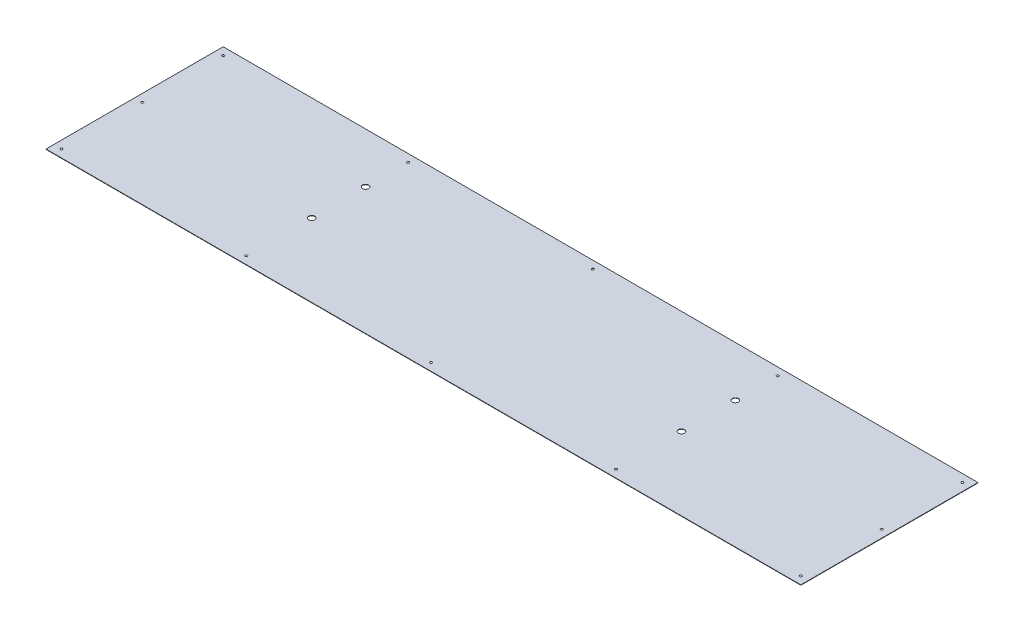
SolidWorks part; units mm, degrees
ref_plane "Front Plane" through (0, 0, 0) normal (0, 0, 1) x (1, 0, 0)
ref_plane "Top Plane" through (0, 0, 0) normal (0, 1, 0) x (1, 0, 0)
ref_plane "Right Plane" through (0, 0, 0) normal (1, 0, 0) x (0, 0, -1)
sketch "Sketch1" plane through (0, 0, 0) normal (0, 1, 0) x (1, 0, 0)
  line L1 (980, 230) -> (-980, 230)
  line L2 (980, 230) -> (980, -230)
  line L3 (980, -230) -> (-980, -230)
  line L4 (-980, 230) -> (-980, -230)
  line L5 (980, 230) -> (-980, -230) construction
  line L6 (980, -230) -> (-980, 230) construction
  point P0 (0, 0)
  dimension "D1" = 460
  dimension "D2" = 1960
extrude "Boss-Extrude1" add sketch "Sketch1" along normal blind 1
ref_plane "Plane1" through (0, 1, 0) normal (0, 1, 0) x (1, 0, 0)
sketch "Sketch2" plane through (0, 1, 0) normal (0, 1, 0) x (1, 0, 0)
  line L0 (0, -210) -> (-960, -210) construction
  line L1 (960, -210) -> (0, -210) construction
  line L2 (960, 210) -> (0, 210) construction
  line L3 (0, 210) -> (-960, 210) construction
  line L4 (-980, 230) -> (-980, -230)
  line L5 (-980, -230) -> (980, -230)
  line L6 (980, -230) -> (980, 230)
  line L7 (980, 230) -> (-980, 230)
  line L8 (-980, 230) -> (-980, -230) construction
  line L9 (-480, 100) -> (480, 100) construction
  line L10 (-480, 100) -> (-480, -40) construction
  line L11 (-980, 100) -> (980, 100) construction
  line L12 (-480, -40) -> (480, -40) construction
  line L13 (-980, -40) -> (980, -40) construction
  line L14 (-980, -230) -> (980, -230) construction
  line L15 (480, -40) -> (480, 100) construction
  line L16 (980, -230) -> (980, 230) construction
  line L17 (980, 230) -> (-980, 230) construction
  circle A0 centre (480, -40) radius 8
  circle A1 centre (-480, -40) radius 8
  circle A2 centre (-480, 100) radius 8
  circle A3 centre (480, 100) radius 8
  circle A4 centre (960, -210) radius 3
  circle A5 centre (-960, -210) radius 3
  circle A6 centre (-960, 210) radius 3
  circle A7 centre (960, 210) radius 3
  circle A8 centre (-960, 0) radius 3
  circle A9 centre (960, 0) radius 3
  circle A10 centre (0, -210) radius 3
  circle A11 centre (0, 210) radius 3
  circle A12 centre (480, -210) radius 3
  circle A13 centre (-480, -210) radius 3
  circle A14 centre (-480, 210) radius 3
  circle A15 centre (480, 210) radius 3
  dimension "D2" = 0
  dimension "D1" = 140
extrude "Cut-Extrude1" cut sketch "Sketch2" against normal through all
chamfer "Chamfer1" distance 1 angle 45 12 edges at (-960, 0, 3) (-960, 0, -207) (-480, 0, -207) (0, 0, -207) (480, 0, -207) (960, 0, -207) (960, 0, 3) (960, 0, 213) (480, 0, 213) (0, 0, 213) (-480, 0, 213) (-960, 0, 213)
